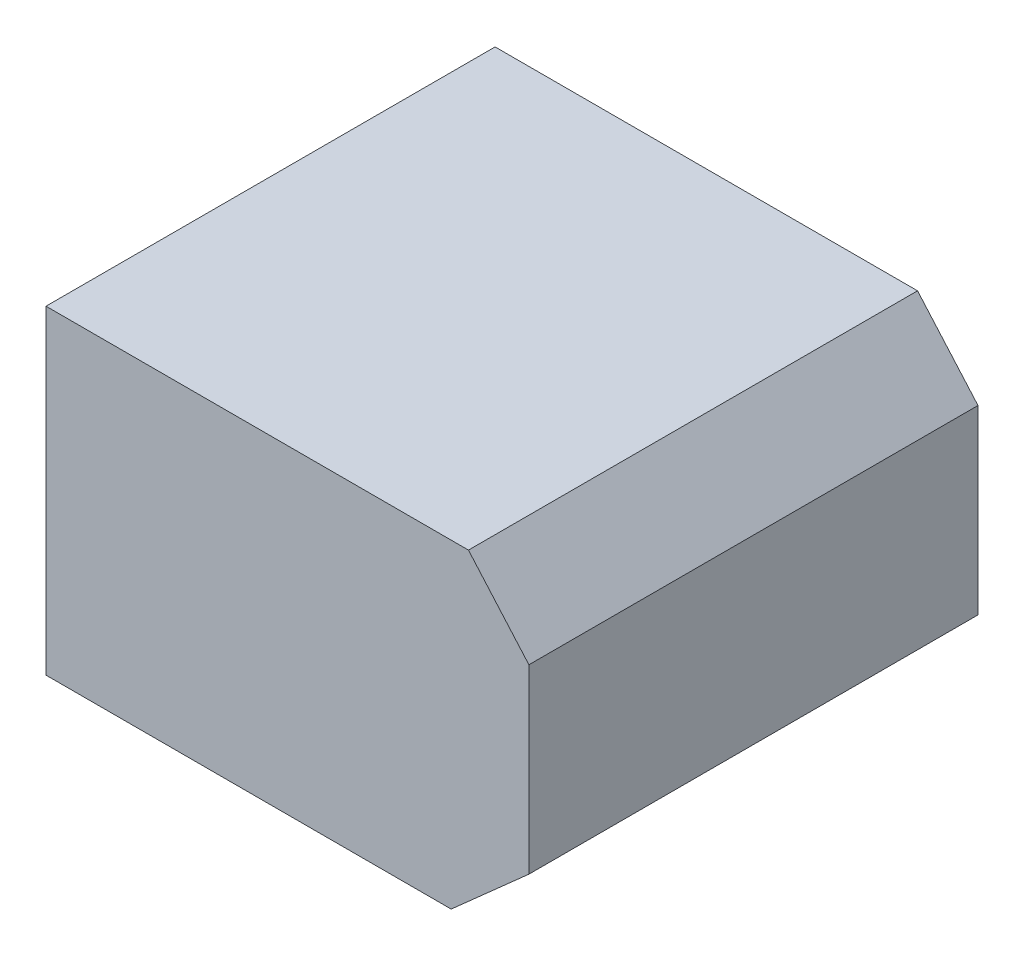
SolidWorks part; units mm, degrees
ref_plane "前视基准面" through (0, 0, 0) normal (0, 0, 1) x (1, 0, 0)
ref_plane "上视基准面" through (0, 0, 0) normal (0, 1, 0) x (1, 0, 0)
ref_plane "右视基准面" through (0, 0, 0) normal (1, 0, 0) x (0, 0, -1)
other "Configuration Table"
sketch "草图1" plane through (0, 0, 0) normal (0, 0, 1) x (1, 0, 0)
  line L0 (-0.9152, 0) -> (48, 0)
  line L1 (48, 0) -> (55, -8)
  line L2 (55, -8) -> (55, -29)
  line L3 (55, -29) -> (46, -37)
  line L4 (46, -37) -> (-0.9152, -37)
  line L5 (-0.9152, -37) -> (-0.9152, 0)
  dimension "x0" = 0.9152
  dimension "x1" = 48
  dimension "x2" = 55
  dimension "x4" = 46
  dimension "y2" = 8
  dimension "y3" = 29
  dimension "y4" = 37
extrude "Closing_lip_profile" add sketch "草图1" along normal blind 52
shell "抽壳1" thickness 5 removed face at (-0.9152, -18.5, 26)
